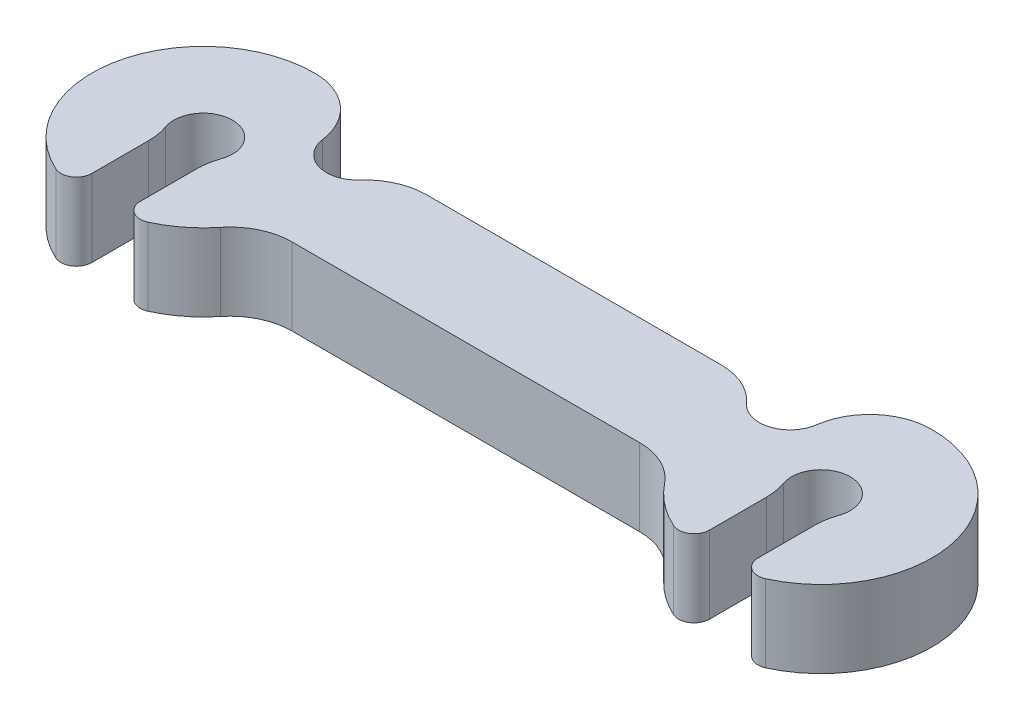
SolidWorks part; units mm, degrees
material "PE hochdicht"
ref_plane "Ebene vorne" through (0, 0, 0) normal (0, 0, 1) x (1, 0, 0)
ref_plane "Ebene oben" through (0, 0, 0) normal (0, 1, 0) x (1, 0, 0)
ref_plane "Ebene rechts" through (0, 0, 0) normal (1, 0, 0) x (0, 0, -1)
sketch "Skizze1" plane through (0, 0, 0) normal (0, 1, 0) x (1, 0, 0)
  line L0 (-10, 0) -> (0, 0) construction
  line L1 (-6.7274, -1.5) -> (0, -1.5)
  line L2 (-7.0067, 2) -> (0, 2)
  line L3 (0, 2) -> (0, -1.5)
  line L4 (-10, 2) -> (0, 2) construction
  line L5 (-10, -1.5) -> (0, -1.5) construction
  circle A0 centre (-10, 0) radius 0.952
  arc A1 (-7.0067, 2) -> (-6.7274, -1.5) centre (-10, 0) ccw
  dimension "D3" = 3.6
  dimension "D4" = 1.904
  dimension "D5" = 10
  dimension "D1" = 1.5
  dimension "D2" = 2
extrude "Aufsatz-Linear austragen1" add sketch "Skizze1" along normal mid plane 2.5
sketch "Skizze2" plane through (0, 1.25, 0) normal (0, 1, 0) x (1, 0, 0)
  line L0 (-10, 0) -> (-10, -3.6) construction
  line L1 (-9.216, 0) -> (-9.216, -3.6)
  line L2 (-10.784, 0) -> (-10.784, -3.6)
  circle A0 centre (-7.0067, 2) radius 1
  arc A1 (-7.0067, 2) -> (-6.7274, -1.5) centre (-10, 0) ccw construction
  arc A2 (-9.216, 0) -> (-10.784, 0) centre (-10, 0) ccw
  arc A3 (-10.784, -3.6) -> (-9.216, -3.6) centre (-10, -3.6) ccw
  point P10 (-10, -1.8)
  dimension "D1" = 2
  dimension "D2" = 1.568
extrude "Schnitt-Linear austragen1" cut sketch "Skizze2" against normal through all
fillet "Verrundung1" radius 2 5 edges at (-10.784, 0, 0.54) (-9.216, 0, 0.54) (-6.0067, 0, -2) (-7.6723, 0, -2.7463) (-6.7274, 0, 1.5)
fillet "Verrundung2" radius 0.5 2 edges at (-9.216, 0, 3.5136) (-10.784, 0, 3.5136)
sketch "Skizze3" plane through (0, 0, 0) normal (0, 0, 1) x (1, 0, 0)
  line L0 (0, 0) -> (-3.8826, 0)
  line L1 (0, 1.25) -> (0, -1.25) construction
  line L2 (-8.5089, 1.25) -> (-9.216, 1.25) construction
  line L4 (-7.1898, 1.25) -> (0, 1.25)
  line L5 (0, 1.25) -> (0, 0)
  arc A0 (-3.8826, 0) -> (-7.1898, 1.25) centre (-3.8826, 5) cw
  dimension "D1" = 5
extrude "Schnitt-Linear austragen2" [suppressed] cut sketch "Skizze3" against normal mid plane 5
fillet "Verrundung3" [suppressed] radius 1
mirror "Spiegeln1" about plane through (0, 1.25, -2) normal (-1, 0, 0) of bodies 103 104
sketch "Skizze4" plane through (0, 1.25, 0) normal (0, 1, 0) x (1, 0, 0)
  circle A0 centre (0, 0) radius 6.2865
  arc A4 (-7.9977, 1.8666) -> (-6.2613, 1.3333) centre (-7.0067, 2) ccw construction
extrude "Aufsatz-Linear austragen2" [suppressed] add sketch "Skizze4" against normal up to surface (4 mm away) up to face at (0, -1.25, 0.5829)
sketch "Skizze5" [suppressed] plane through (0, 2, 0) normal (0, 1, 0) x (1, 0, 0)
  circle A0 centre (0, 0) radius 4.5
  dimension "D1" = 9
extrude "Schnitt-Linear austragen3" [suppressed] cut sketch "Skizze5" against normal through all
fillet "Verrundung4" [suppressed] radius 1
